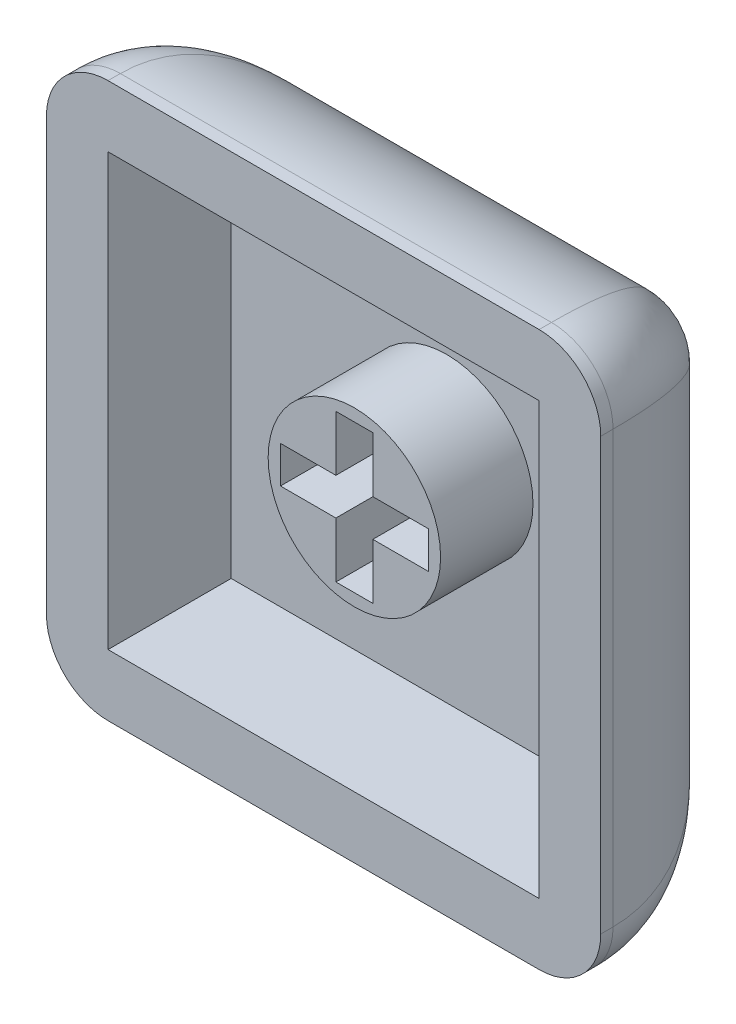
SolidWorks part; units mm, degrees
ref_plane "前视基准面" through (0, 0, 0) normal (0, 0, 1) x (1, 0, 0)
ref_plane "上视基准面" through (0, 0, 0) normal (0, 1, 0) x (1, 0, 0)
ref_plane "右视基准面" through (0, 0, 0) normal (1, 0, 0) x (0, 0, -1)
other "Configuration Table"
sketch "草图1" plane through (0, 0, 0) normal (0, 0, 1) x (1, 0, 0)
  line L1 (-7, -9) -> (7, -9)
  line L2 (-9, -7) -> (-9, 7)
  line L3 (-7, 9) -> (7, 9)
  line L4 (9, -7) -> (9, 7)
  line L5 (-9, -9) -> (9, 9) construction
  line L6 (-9, 9) -> (9, -9) construction
  arc A0 (7, -9) -> (9, -7) centre (7, -7) ccw
  arc A1 (-7, -9) -> (-9, -7) centre (-7, -7) cw
  arc A2 (7, 9) -> (9, 7) centre (7, 7) cw
  arc A3 (-9, 7) -> (-7, 9) centre (-7, 7) cw
  point P0 (0, 0)
  dimension "D1" = 2
  dimension "D2" = 18
extrude "凸台-拉伸1" add sketch "草图1" along normal blind 6.4 contours L3 A2 L4 A0 L1 A1 L2 A3
sketch "草图2" plane through (0, 0, 6.4) normal (0, 0, 1) x (1, 0, 0)
  line L4 (-9, 7) -> (-9, -7)
  line L5 (-7, -9) -> (7, -9)
  line L6 (9, -7) -> (9, 7)
  line L7 (7, 9) -> (-7, 9)
  line L8 (-9, 7) -> (-9, -7)
  line L9 (-7, -9) -> (7, -9)
  line L10 (9, -7) -> (9, 7)
  line L11 (7, 9) -> (-7, 9)
  arc A4 (-7, 9) -> (-9, 7) centre (-7, 7) ccw
  arc A5 (-9, -7) -> (-7, -9) centre (-7, -7) ccw
  arc A6 (7, -9) -> (9, -7) centre (7, -7) ccw
  arc A7 (9, 7) -> (7, 9) centre (7, 7) ccw
  arc A8 (-7, 9) -> (-9, 7) centre (-7, 7) ccw
  arc A9 (-9, -7) -> (-7, -9) centre (-7, -7) ccw
  arc A10 (7, -9) -> (9, -7) centre (7, -7) ccw
  arc A11 (9, 7) -> (7, 9) centre (7, 7) ccw
  dimension "D1" = 0
extrude "拉伸-薄壁1" [suppressed] add sketch "草图2" along normal blind 5 thin thin type one direction reverse wall 2
sketch "草图3" plane through (0, 0, 6.4) normal (0, 0, 1) x (1, 0, 0)
  line L0 (-2.8, 0) -> (2.8, 0) construction
  line L1 (0, 2.8) -> (0, -2.8) construction
  line L2 (0, 2.4) -> (-0.6, 2.4)
  line L3 (-0.6, 2.4) -> (-0.6, 0.6)
  line L4 (-0.6, 0.6) -> (-2.4, 0.6)
  line L5 (-2.4, 0.6) -> (-2.4, 0)
  line L6 (2.4, 0) -> (2.4, 0.6)
  line L7 (2.4, 0.6) -> (0.6, 0.6)
  line L8 (0.6, 0.6) -> (0.6, 2.4)
  line L9 (0.6, 2.4) -> (0, 2.4)
  line L10 (0, -2.4) -> (0.6, -2.4)
  line L11 (0.6, -2.4) -> (0.6, -0.6)
  line L12 (0.6, -0.6) -> (2.4, -0.6)
  line L13 (2.4, -0.6) -> (2.4, 0)
  line L14 (-2.4, 0) -> (-2.4, -0.6)
  line L15 (-2.4, -0.6) -> (-0.6, -0.6)
  line L16 (-0.6, -0.6) -> (-0.6, -2.4)
  line L17 (-0.6, -2.4) -> (0, -2.4)
  line L26 (-7, 7) -> (-7, -7)
  line L27 (-7, -7) -> (7, -7)
  line L28 (7, -7) -> (7, 7)
  line L29 (7, 7) -> (-7, 7)
  line L30 (-7, 7) -> (-7, -7)
  line L31 (-7, -7) -> (7, -7)
  line L32 (7, -7) -> (7, 7)
  line L33 (7, 7) -> (-7, 7)
  circle A0 centre (0, 0) radius 2.8
  point P10 (0, 0)
  point P13 (0, 0)
  point P30 (0, 0)
  dimension "D1" = 5.6
  dimension "D3" = 4.8
  dimension "D4" = 1.2
  dimension "D5" = 2
  dimension "D2" = 4
fillet "圆角1" radius 6 8 edges at (-9, 0, 0) (-8.4142, -8.4142, 0) (0, -9, 0) (8.4142, -8.4142, 0) (9, 0, 0) (8.4142, 8.4142, 0) (0, 9, 0) (-8.4142, 8.4142, 0)
extrude "切除-拉伸1" cut sketch "草图3" against normal blind 4 contours L32 L33 L30 L31 A0 | L16 L17 L10 L11 L12 L13 L6 L7 L8 L9 L2 L3 L4 L5 L14 L15 region at (0, 0, 6.4) region at (0, 6.802, 6.4)
sketch "草图4" plane through (0, 0, 6.4) normal (0, 0, 1) x (1, 0, 0)
  circle A1 centre (0, 0) radius 2.8
  circle A2 centre (0, 0) radius 2.8
  dimension "D1" = 0
extrude "切除-拉伸2" cut sketch "草图4" against normal blind 1
